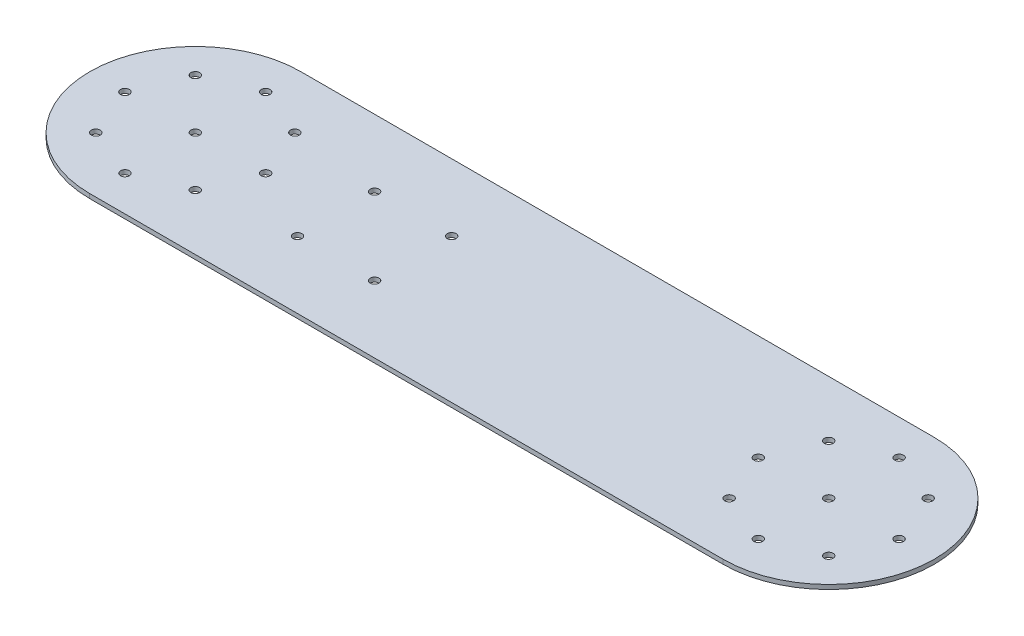
SolidWorks part; units mm, degrees
ref_plane "Front Plane" through (0, 0, 0) normal (0, 0, 1) x (1, 0, 0)
ref_plane "Top Plane" through (0, 0, 0) normal (0, 1, 0) x (1, 0, 0)
ref_plane "Right Plane" through (0, 0, 0) normal (1, 0, 0) x (0, 0, -1)
sketch "Sketch1" plane through (0, 0, 0) normal (0, 1, 0) x (1, 0, 0)
  line L0 (0, 0) -> (0, 171.3006) construction
  line L1 (-228.6, -76.2) -> (228.6, -76.2)
  line L3 (-228.6, 76.2) -> (228.6, 76.2)
  line L5 (-228.6, -76.2) -> (228.6, 76.2) construction
  line L6 (-228.6, 76.2) -> (228.6, -76.2) construction
  arc A1 (-228.6, 76.2) -> (-228.6, -76.2) centre (-228.6, 0) ccw
  arc A4 (228.6, 76.2) -> (228.6, -76.2) centre (228.6, 0) cw
  circle A20 centre (-127, 27.813) radius 3.175
  circle A21 centre (-127, -27.813) radius 3.175
  circle A23 centre (-71.374, -27.813) radius 3.175
  circle A24 centre (-71.374, 27.813) radius 3.175
  point P0 (0, 0)
  point P38 (-228.6, 0)
  point P41 (-304.8, 0)
  point P62 (-304.8, 0)
  point P71 (304.8, 0)
  dimension "D4" = 76.2
  dimension "D7" = 6.35
  dimension "D1" = 152.4
  dimension "D2" = 457.2
  dimension "D9" = 27.813
  dimension "D11" = 55.626
  dimension "D8" = 55.626
  dimension "D10" = 127
extrude "Boss-Extrude1" add sketch "Sketch1" along normal blind 3.175
sketch "Sketch3" plane through (0, 3.175, 0) normal (0, 1, 0) x (1, 0, 0)
  circle A0 centre (-228.6, 50.8) radius 3.175
  circle A3 centre (-127, 27.813) radius 3.175 construction
  circle A4 centre (-228.6, 0) radius 3.175
  arc A5 (-228.6, 76.2) -> (-228.6, -76.2) centre (-228.6, 0) ccw construction
  dimension "D1" = 50.8
extrude "Cut-Extrude1" cut sketch "Sketch3" against normal through all
pattern_circular "CirPattern1" count 8 over 360 about axis through (-228.6, 0, 0) along (0, 1, 0) of "Cut-Extrude1"
mirror "Mirror1" about plane through (0, 0, 0) normal (1, 0, 0) of "CirPattern1"
equation "\"D4@Sketch1\"= 0.5 * \"D1@Sketch1\""
equation "\"D9@Sketch1\"= 0.5 * \"D11@Sketch1\""
equation "\"D8@Sketch1\"= \"D11@Sketch1\""
